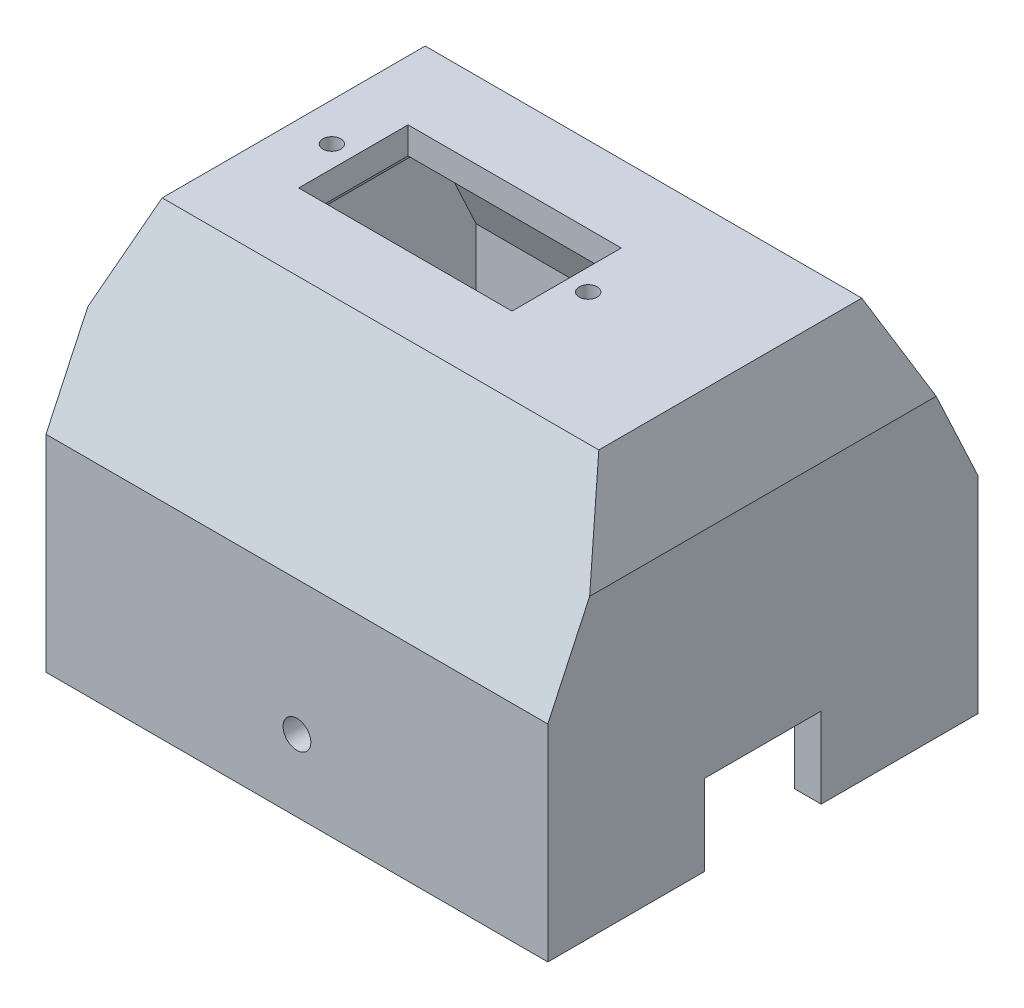
SolidWorks part; units mm, degrees
ref_plane "前视基准面" through (0, 0, 0) normal (0, 0, 1) x (1, 0, 0)
ref_plane "上视基准面" through (0, 0, 0) normal (0, 1, 0) x (1, 0, 0)
ref_plane "右视基准面" through (0, 0, 0) normal (1, 0, 0) x (0, 0, -1)
sketch "草图47" plane through (0, 0, 0) normal (0, 1, 0) x (1, 0, 0)
  line L1 (28, -24) -> (-28, -24)
  line L2 (28, -24) -> (28, 24)
  line L3 (28, 24) -> (-28, 24)
  line L4 (-28, -24) -> (-28, 24)
  line L5 (28, -24) -> (-28, 24) construction
  line L6 (28, 24) -> (-28, -24) construction
  point P0 (0, 0)
  dimension "D1" = 48
  dimension "D2" = 56
extrude "凸台-拉伸4" add sketch "草图47" along normal blind 43
chamfer "倒角1" distance 10 angle 20 2 edges at (28, 43, 0) (-28, 43, 0) first distance on face at (28, 21.5, 0) first distance on face at (-28, 21.5, 0)
chamfer "倒角2" distance 20 angle 25 2 edges at (0, 43, -24) (0, 43, 24) first distance on face at (0, 25.3333, -24) first distance on face at (0, 25.3333, 24)
shell "抽壳1" thickness 3 removed face at (0, 0, 0)
sketch "草图48" plane through (0, 43, -43) normal (0, -1, 0) x (1, 0, 0)
  line L0 (-5.8, 47.679) -> (-5.8, 60.2141) construction
  line L1 (6.1, 36.9) -> (-17.7, 36.9)
  line L2 (6.1, 36.9) -> (6.1, 49.1)
  line L3 (6.1, 49.1) -> (-17.7, 49.1)
  line L4 (-17.7, 36.9) -> (-17.7, 49.1)
  line L5 (6.1, 36.9) -> (-17.7, 49.1) construction
  line L6 (6.1, 49.1) -> (-17.7, 36.9) construction
  line L13 (-20.1, 43) -> (-5.8, 43) construction
  circle A0 centre (-20.1, 43) radius 1
  circle A2 centre (8.5, 43) radius 1
  circle A3 centre (0, 43) radius 6.1 construction
  point P0 (-5.8, 43)
  point P6 (-5.8, 43)
  point P10 (0, 43)
  dimension "D4" = 2
  dimension "D1" = 23.8
  dimension "D2" = 12.2
  dimension "D3" = 14.3
extrude "切除-拉伸3" cut sketch "草图48" along normal up to next
sketch "草图49" plane through (0, 0, -24) normal (0, 0, -1) x (-1, 0, 0)
  line L0 (-28, 0) -> (28, 0) construction
  circle A0 centre (0, 8) radius 1.55
  point P4 (0, 0)
  dimension "D1" = 3.1
  dimension "D2" = 8
extrude "切除-拉伸4" cut sketch "草图49" against normal through all
sketch "草图50" plane through (28, 0, 0) normal (1, 0, 0) x (0, 0, -1)
  line L0 (-24, 0) -> (24, 0) construction
  line L1 (6.5, 9) -> (-6.5, 9)
  line L2 (6.5, 9) -> (6.5, 0)
  line L3 (6.5, 0) -> (-6.5, 0)
  line L4 (-6.5, 9) -> (-6.5, 0)
  line L5 (6.5, 9) -> (-6.5, 0) construction
  line L6 (6.5, 0) -> (-6.5, 9) construction
  point P0 (0, 4.5)
  dimension "D1" = 9
  dimension "D2" = 13
extrude "切除-拉伸5" cut sketch "草图50" against normal up to next
sketch "草图51" plane through (-28, 0, 0) normal (-1, 0, 0) x (0, 0, 1)
  line L0 (-24, 0) -> (24, 0) construction
  line L1 (5.3596, 21.8798) -> (-5.3596, 21.8798)
  line L2 (5.3596, 21.8798) -> (5.3596, 0)
  line L3 (5.3596, 0) -> (-5.3596, 0)
  line L4 (-5.3596, 21.8798) -> (-5.3596, 0)
  line L5 (5.3596, 21.8798) -> (-5.3596, 0) construction
  line L6 (5.3596, 0) -> (-5.3596, 21.8798) construction
  point P0 (0, 10.9399)
extrude "切除-拉伸6" cut sketch "草图51" against normal up to next
